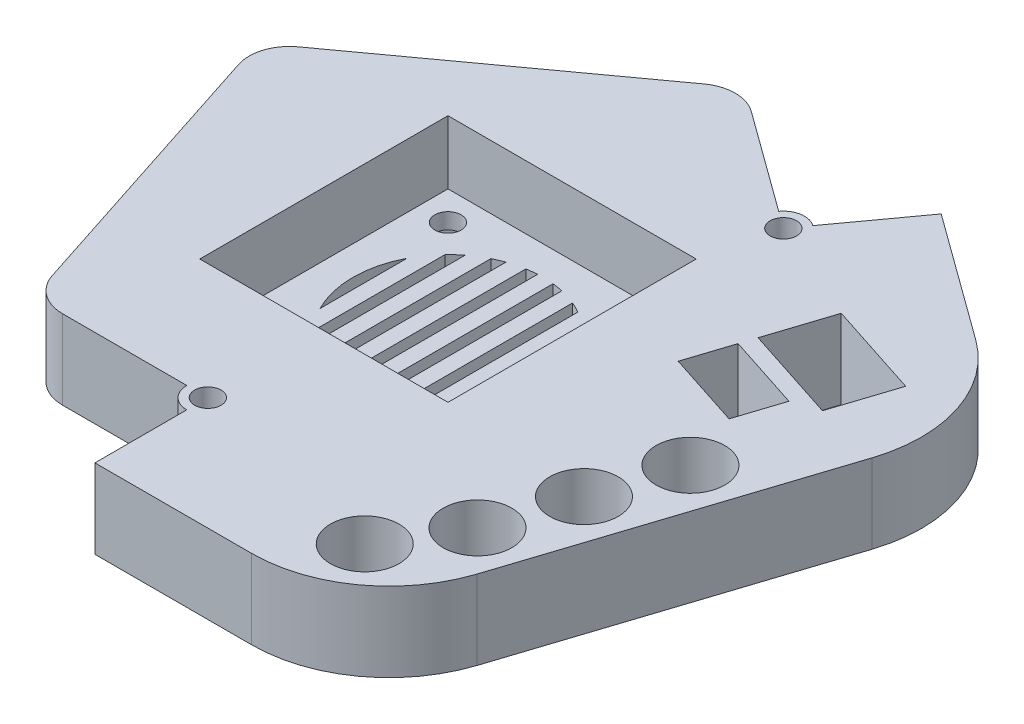
SolidWorks part; units mm, degrees
material "ABS"
ref_plane "Front Plane" through (0, 0, 0) normal (0, 0, 1) x (1, 0, 0)
ref_plane "Top Plane" through (0, 0, 0) normal (0, 1, 0) x (1, 0, 0)
ref_plane "Right Plane" through (0, 0, 0) normal (1, 0, 0) x (0, 0, -1)
sketch "Sketch1" plane through (0, 0, 0) normal (0, 1, 0) x (1, 0, 0)
  line L0 (-12.5926, 0) -> (122.24, 0) construction
  line L1 (-76.5046, 8.789) -> (-56.7275, -52.0787)
  line L2 (-32, -70.0442) -> (32, -70.0442)
  line L3 (56.7275, -52.0787) -> (76.5046, 8.789)
  line L4 (67.0595, 37.8578) -> (15.2824, 75.4761)
  line L5 (-15.2824, 75.4761) -> (-67.0595, 37.8578)
  line L7 (-72.7662, 7.5743) -> (-54.4171, -48.8987)
  line L8 (-29.6896, -66.8642) -> (29.6896, -66.8642)
  line L9 (54.4171, -48.8987) -> (72.7662, 7.5743)
  line L10 (63.3212, 36.6432) -> (15.2824, 71.5454)
  line L11 (-15.2824, 71.5454) -> (-63.3212, 36.6432)
  line L12 (-39.9799, 8.2808) -> (-27.4771, -30.1989)
  line L13 (-20.23, -35.4642) -> (20.23, -35.4642)
  line L14 (27.4771, -30.1989) -> (39.9799, 8.2808)
  line L15 (37.2118, 16.8002) -> (4.4789, 40.582)
  line L16 (-4.4789, 40.582) -> (-37.2118, 16.8002)
  line L17 (-34.7536, 6.5827) -> (-24.2471, -25.7532)
  line L18 (-17, -31.0185) -> (17, -31.0185)
  line L19 (24.2471, -25.7532) -> (34.7536, 6.5827)
  line L20 (31.9855, 15.1021) -> (4.4789, 35.0868)
  line L21 (-4.4789, 35.0868) -> (-31.9855, 15.1021)
  line L22 (-31.0153, 5.3681) -> (-21.9366, -22.5732)
  line L23 (-14.6896, -27.8385) -> (14.6896, -27.8385)
  line L24 (21.9366, -22.5732) -> (31.0153, 5.3681)
  line L25 (28.2472, 13.8875) -> (4.4789, 31.1561)
  line L26 (-4.4789, 31.1561) -> (-28.2472, 13.8875)
  circle A0 centre (0, 0) radius 70.0442 construction
  arc A1 (-56.7275, -52.0787) -> (-32, -70.0442) centre (-32, -44.0442) ccw
  arc A2 (32, -70.0442) -> (56.7275, -52.0787) centre (32, -44.0442) ccw
  arc A3 (76.5046, 8.789) -> (67.0595, 37.8578) centre (51.7771, 16.8234) ccw
  arc A4 (15.2824, 75.4761) -> (-15.2824, 75.4761) centre (0, 54.4417) ccw
  arc A5 (-76.5046, 8.789) -> (-67.0595, 37.8578) centre (-51.7771, 16.8234) cw
  circle A6 centre (0, 0) radius 66.8642 construction
  arc A7 (15.2824, 71.5454) -> (-15.2824, 71.5454) centre (0, 50.511) ccw
  arc A8 (72.7662, 7.5743) -> (63.3212, 36.6432) centre (48.0388, 15.6087) ccw
  arc A9 (29.6896, -66.8642) -> (54.4171, -48.8987) centre (29.6896, -40.8642) ccw
  arc A10 (-72.7662, 7.5743) -> (-63.3212, 36.6432) centre (-48.0388, 15.6087) cw
  arc A11 (-54.4171, -48.8987) -> (-29.6896, -66.8642) centre (-29.6896, -40.8642) ccw
  circle A12 centre (0, 0) radius 35.4642 construction
  circle A13 centre (0, 0) radius 31.0185 construction
  arc A14 (-24.2471, -25.7532) -> (-17, -31.0185) centre (-17, -23.3985) ccw
  arc A15 (17, -31.0185) -> (24.2471, -25.7532) centre (17, -23.3985) ccw
  arc A16 (34.7536, 6.5827) -> (31.9855, 15.1021) centre (27.5066, 8.9374) ccw
  arc A17 (4.4789, 35.0868) -> (-4.4789, 35.0868) centre (0, 28.9221) ccw
  arc A18 (4.4789, 40.582) -> (-4.4789, 40.582) centre (0, 34.4173) ccw
  arc A19 (39.9799, 8.2808) -> (37.2118, 16.8002) centre (32.7328, 10.6355) ccw
  arc A20 (20.23, -35.4642) -> (27.4771, -30.1989) centre (20.23, -27.8442) ccw
  arc A21 (-27.4771, -30.1989) -> (-20.23, -35.4642) centre (-20.23, -27.8442) ccw
  arc A22 (-39.9799, 8.2808) -> (-37.2118, 16.8002) centre (-32.7328, 10.6355) cw
  arc A23 (-34.7536, 6.5827) -> (-31.9855, 15.1021) centre (-27.5066, 8.9374) cw
  circle A24 centre (0, 0) radius 27.8385 construction
  arc A25 (-21.9366, -22.5732) -> (-14.6896, -27.8385) centre (-14.6896, -20.2185) ccw
  arc A26 (14.6896, -27.8385) -> (21.9366, -22.5732) centre (14.6896, -20.2185) ccw
  arc A27 (31.0153, 5.3681) -> (28.2472, 13.8875) centre (23.7683, 7.7228) ccw
  arc A28 (4.4789, 31.1561) -> (-4.4789, 31.1561) centre (0, 24.9914) ccw
  arc A29 (-31.0153, 5.3681) -> (-28.2472, 13.8875) centre (-23.7683, 7.7228) cw
  dimension "D1" = 26
  dimension "D3" = 26
  dimension "D5" = 7.62
  dimension "D8" = 7.62
  dimension "D2" = 64
  dimension "D4" = 3.18
  dimension "D6" = 40.46
  dimension "D7" = 34
  dimension "D9" = 3.18
extrude "Boss-Extrude1" add sketch "Sketch1" along normal blind 10 contours A23 L17 A14 L18 A15 L19 A16 L20 A17 L21 L22 A29 L26 A28 L25 A27 L24 A26 L23 A25 region at (-33.8267, 0, -10.9909)
sketch "Sketch2" plane through (0, 0, 0) normal (0, -1, 0) x (1, 0, 0)
  line L15 (-54.4171, 48.8987) -> (-72.7662, -7.5743)
  line L16 (29.6896, 66.8642) -> (-29.6896, 66.8642)
  line L17 (72.7662, -7.5743) -> (54.4171, 48.8987)
  line L18 (15.2824, -71.5454) -> (63.3212, -36.6432)
  line L19 (-63.3212, -36.6432) -> (-15.2824, -71.5454)
  line L20 (-54.4171, 48.8987) -> (-72.7662, -7.5743)
  line L21 (29.6896, 66.8642) -> (-29.6896, 66.8642)
  line L22 (72.7662, -7.5743) -> (54.4171, 48.8987)
  line L23 (15.2824, -71.5454) -> (63.3212, -36.6432)
  line L24 (-63.3212, -36.6432) -> (-15.2824, -71.5454)
  line L25 (-24.2471, 25.7532) -> (-34.7536, -6.5827)
  line L26 (17, 31.0185) -> (-17, 31.0185)
  line L27 (34.7536, -6.5827) -> (24.2471, 25.7532)
  line L28 (4.4789, -35.0868) -> (31.9855, -15.1021)
  line L29 (-31.9855, -15.1021) -> (-4.4789, -35.0868)
  line L30 (-24.2471, 25.7532) -> (-34.7536, -6.5827)
  line L31 (17, 31.0185) -> (-17, 31.0185)
  line L32 (34.7536, -6.5827) -> (24.2471, 25.7532)
  line L33 (4.4789, -35.0868) -> (31.9855, -15.1021)
  line L34 (-31.9855, -15.1021) -> (-4.4789, -35.0868)
  line L35 (-27.4771, 30.1989) -> (-39.9799, -8.2808)
  line L36 (20.23, 35.4642) -> (-20.23, 35.4642)
  line L37 (39.9799, -8.2808) -> (27.4771, 30.1989)
  line L38 (4.4789, -40.582) -> (37.2118, -16.8002)
  line L39 (-37.2118, -16.8002) -> (-4.4789, -40.582)
  line L40 (-27.4771, 30.1989) -> (-39.9799, -8.2808)
  line L41 (20.23, 35.4642) -> (-20.23, 35.4642)
  line L42 (39.9799, -8.2808) -> (27.4771, 30.1989)
  line L43 (4.4789, -40.582) -> (37.2118, -16.8002)
  line L44 (-37.2118, -16.8002) -> (-4.4789, -40.582)
  line L45 (-21.9366, 22.5732) -> (-31.0153, -5.3681)
  line L46 (14.6896, 27.8385) -> (-14.6896, 27.8385)
  line L47 (31.0153, -5.3681) -> (21.9366, 22.5732)
  line L48 (4.4789, -31.1561) -> (28.2472, -13.8875)
  line L49 (-28.2472, -13.8875) -> (-4.4789, -31.1561)
  line L50 (-21.9366, 22.5732) -> (-31.0153, -5.3681)
  line L51 (14.6896, 27.8385) -> (-14.6896, 27.8385)
  line L52 (31.0153, -5.3681) -> (21.9366, 22.5732)
  line L53 (4.4789, -31.1561) -> (28.2472, -13.8875)
  line L54 (-28.2472, -13.8875) -> (-4.4789, -31.1561)
  arc A15 (-29.6896, 66.8642) -> (-54.4171, 48.8987) centre (-29.6896, 40.8642) ccw
  arc A16 (54.4171, 48.8987) -> (29.6896, 66.8642) centre (29.6896, 40.8642) ccw
  arc A17 (63.3212, -36.6432) -> (72.7662, -7.5743) centre (48.0388, -15.6087) ccw
  arc A18 (-15.2824, -71.5454) -> (15.2824, -71.5454) centre (0, -50.511) ccw
  arc A19 (-72.7662, -7.5743) -> (-63.3212, -36.6432) centre (-48.0388, -15.6087) ccw
  arc A20 (-29.6896, 66.8642) -> (-54.4171, 48.8987) centre (-29.6896, 40.8642) ccw
  arc A21 (54.4171, 48.8987) -> (29.6896, 66.8642) centre (29.6896, 40.8642) ccw
  arc A22 (63.3212, -36.6432) -> (72.7662, -7.5743) centre (48.0388, -15.6087) ccw
  arc A23 (-15.2824, -71.5454) -> (15.2824, -71.5454) centre (0, -50.511) ccw
  arc A24 (-72.7662, -7.5743) -> (-63.3212, -36.6432) centre (-48.0388, -15.6087) ccw
  arc A25 (-17, 31.0185) -> (-24.2471, 25.7532) centre (-17, 23.3985) ccw
  arc A26 (24.2471, 25.7532) -> (17, 31.0185) centre (17, 23.3985) ccw
  arc A27 (31.9855, -15.1021) -> (34.7536, -6.5827) centre (27.5066, -8.9374) ccw
  arc A28 (-4.4789, -35.0868) -> (4.4789, -35.0868) centre (0, -28.9221) ccw
  arc A29 (-34.7536, -6.5827) -> (-31.9855, -15.1021) centre (-27.5066, -8.9374) ccw
  arc A30 (-17, 31.0185) -> (-24.2471, 25.7532) centre (-17, 23.3985) ccw
  arc A31 (24.2471, 25.7532) -> (17, 31.0185) centre (17, 23.3985) ccw
  arc A32 (31.9855, -15.1021) -> (34.7536, -6.5827) centre (27.5066, -8.9374) ccw
  arc A33 (-4.4789, -35.0868) -> (4.4789, -35.0868) centre (0, -28.9221) ccw
  arc A34 (-34.7536, -6.5827) -> (-31.9855, -15.1021) centre (-27.5066, -8.9374) ccw
  arc A35 (-20.23, 35.4642) -> (-27.4771, 30.1989) centre (-20.23, 27.8442) ccw
  arc A36 (27.4771, 30.1989) -> (20.23, 35.4642) centre (20.23, 27.8442) ccw
  arc A37 (37.2118, -16.8002) -> (39.9799, -8.2808) centre (32.7328, -10.6355) ccw
  arc A38 (-4.4789, -40.582) -> (4.4789, -40.582) centre (0, -34.4173) ccw
  arc A39 (-39.9799, -8.2808) -> (-37.2118, -16.8002) centre (-32.7328, -10.6355) ccw
  arc A40 (-20.23, 35.4642) -> (-27.4771, 30.1989) centre (-20.23, 27.8442) ccw
  arc A41 (27.4771, 30.1989) -> (20.23, 35.4642) centre (20.23, 27.8442) ccw
  arc A42 (37.2118, -16.8002) -> (39.9799, -8.2808) centre (32.7328, -10.6355) ccw
  arc A43 (-4.4789, -40.582) -> (4.4789, -40.582) centre (0, -34.4173) ccw
  arc A44 (-39.9799, -8.2808) -> (-37.2118, -16.8002) centre (-32.7328, -10.6355) ccw
  arc A45 (-14.6896, 27.8385) -> (-21.9366, 22.5732) centre (-14.6896, 20.2185) ccw
  arc A46 (21.9366, 22.5732) -> (14.6896, 27.8385) centre (14.6896, 20.2185) ccw
  arc A47 (28.2472, -13.8875) -> (31.0153, -5.3681) centre (23.7683, -7.7228) ccw
  arc A48 (-4.4789, -31.1561) -> (4.4789, -31.1561) centre (0, -24.9914) ccw
  arc A49 (-31.0153, -5.3681) -> (-28.2472, -13.8875) centre (-23.7683, -7.7228) ccw
  arc A50 (-14.6896, 27.8385) -> (-21.9366, 22.5732) centre (-14.6896, 20.2185) ccw
  arc A51 (21.9366, 22.5732) -> (14.6896, 27.8385) centre (14.6896, 20.2185) ccw
  arc A52 (28.2472, -13.8875) -> (31.0153, -5.3681) centre (23.7683, -7.7228) ccw
  arc A53 (-4.4789, -31.1561) -> (4.4789, -31.1561) centre (0, -24.9914) ccw
  arc A54 (-31.0153, -5.3681) -> (-28.2472, -13.8875) centre (-23.7683, -7.7228) ccw
  arc M51 (-34.7536, -6.5827) -> (-31.9855, -15.1021) centre (-27.5066, -8.9374) ccw
  line M52 (-31.9855, -15.1021) -> (-4.4789, -35.0868)
  arc M53 (-4.4789, -35.0868) -> (4.4789, -35.0868) centre (0, -28.9221) ccw
  line M54 (4.4789, -35.0868) -> (31.9855, -15.1021)
  arc M55 (31.9855, -15.1021) -> (34.7536, -6.5827) centre (27.5066, -8.9374) ccw
  line M56 (34.7536, -6.5827) -> (24.2471, 25.7532)
  arc M57 (24.2471, 25.7532) -> (17, 31.0185) centre (17, 23.3985) ccw
  line M58 (17, 31.0185) -> (-17, 31.0185)
  arc M59 (-17, 31.0185) -> (-24.2471, 25.7532) centre (-17, 23.3985) ccw
  line M60 (-24.2471, 25.7532) -> (-34.7536, -6.5827)
  line M61 (-31.0153, -5.3681) -> (-21.9366, 22.5732)
  arc M62 (-21.9366, 22.5732) -> (-14.6896, 27.8385) centre (-14.6896, 20.2185) cw
  line M63 (-14.6896, 27.8385) -> (14.6896, 27.8385)
  arc M64 (14.6896, 27.8385) -> (21.9366, 22.5732) centre (14.6896, 20.2185) cw
  line M65 (21.9366, 22.5732) -> (31.0153, -5.3681)
  arc M66 (31.0153, -5.3681) -> (28.2472, -13.8875) centre (23.7683, -7.7228) cw
  line M67 (28.2472, -13.8875) -> (4.4789, -31.1561)
  arc M68 (4.4789, -31.1561) -> (-4.4789, -31.1561) centre (0, -24.9914) cw
  line M69 (-4.4789, -31.1561) -> (-28.2472, -13.8875)
  arc M70 (-28.2472, -13.8875) -> (-31.0153, -5.3681) centre (-23.7683, -7.7228) cw
  dimension "D2" = 0
  dimension "D3" = 0
  dimension "D4" = 0
  dimension "D5" = 0
extrude "Boss-Extrude2" add sketch "Sketch2" against normal blind 5 contours L20 A24 L24 A23 L23 A22 L22 A21 L21 A20 A44 L40 A40 L41 A41 L42 A42 L43 A43 L44 | A24 L20 A20 L21 A21 L22 A22 L23 A23 L24 | M61 M70 M69 M68 M67 M66 M65 M64 M63 M62 | L40 A44 L44 A43 L43 A42 L42 A41 L41 A40 M51 M60 M59 M58 M57 M56 M55 M54 M53 M52 region at (-43.7605, 0, 60.2312) region at (-24.0512, 0, 33.1037) region at (0, 0, 0)
sketch "Sketch4" plane through (0, 5, 0) normal (0, 1, 0) x (1, 0, 0)
  line L0 (26.7257, 36.7848) -> (39.3018, 54.0943)
  line L1 (-4.4789, 52.948) -> (-48.9725, 20.6215)
  line L2 (-51.7406, 12.1021) -> (-34.7456, -40.2032)
  line L3 (-27.4985, -45.4685) -> (0, -45.4685)
  line L5 (-15.2824, 71.5454) -> (-63.3212, 36.6432)
  line L6 (63.3212, 36.6432) -> (15.2824, 71.5454)
  line L7 (54.4171, -48.8987) -> (72.7662, 7.5743)
  line L8 (-29.6896, -66.8642) -> (29.6896, -66.8642)
  line L9 (-72.7662, 7.5743) -> (-54.4171, -48.8987)
  line L11 (63.3212, 36.6432) -> (39.3018, 54.0943)
  line L12 (54.4171, -48.8987) -> (72.7662, 7.5743)
  line L13 (0, -66.8642) -> (29.6896, -66.8642)
  line L17 (-31.9855, 15.1021) -> (-4.4789, 35.0868) construction
  line L45 (26.7257, 36.7848) -> (4.4789, 52.948)
  line L46 (0, -45.4685) -> (0, -66.8642)
  line L47 (-54.4171, -48.8987) -> (-72.7662, 7.5743) construction
  line L48 (-63.3212, 36.6432) -> (-15.2824, 71.5454) construction
  line L49 (-54.4171, -48.8987) -> (-72.7662, 7.5743)
  line L50 (-63.3212, 36.6432) -> (-15.2824, 71.5454)
  line L51 (39.3018, 54.0943) -> (15.2824, 71.5454)
  line L52 (-29.6896, -66.8642) -> (0, -66.8642)
  line L58 (39.5946, -25.2793) -> (54.3426, 20.1102) [skipped]
  arc A1 (-4.4789, 52.948) -> (4.4789, 52.948) centre (0, 46.7833) cw
  arc A2 (-48.9725, 20.6215) -> (-51.7406, 12.1021) centre (-44.4936, 14.4568) ccw
  arc A3 (-34.7456, -40.2032) -> (-27.4985, -45.4685) centre (-27.4985, -37.8485) ccw
  arc A5 (15.2824, 71.5454) -> (-15.2824, 71.5454) centre (0, 50.511) ccw
  arc A6 (72.7662, 7.5743) -> (63.3212, 36.6432) centre (48.0388, 15.6087) ccw
  arc A7 (29.6896, -66.8642) -> (54.4171, -48.8987) centre (29.6896, -40.8642) ccw
  arc A8 (-54.4171, -48.8987) -> (-29.6896, -66.8642) centre (-29.6896, -40.8642) ccw
  arc A9 (-63.3212, 36.6432) -> (-72.7662, 7.5743) centre (-48.0388, 15.6087) ccw
  arc A11 (72.7662, 7.5743) -> (63.3212, 36.6432) centre (48.0388, 15.6087) ccw
  arc A12 (29.6896, -66.8642) -> (54.4171, -48.8987) centre (29.6896, -40.8642) ccw
  arc A46 (-54.4171, -48.8987) -> (-29.6896, -66.8642) centre (-29.6896, -40.8642) ccw construction
  arc A47 (-63.3212, 36.6432) -> (-72.7662, 7.5743) centre (-48.0388, 15.6087) ccw construction
  arc A48 (15.2824, 71.5454) -> (-15.2824, 71.5454) centre (0, 50.511) ccw construction
  arc A49 (-54.4171, -48.8987) -> (-29.6896, -66.8642) centre (-29.6896, -40.8642) ccw
  arc A50 (-63.3212, 36.6432) -> (-72.7662, 7.5743) centre (-48.0388, 15.6087) ccw
  arc A51 (15.2824, 71.5454) -> (-15.2824, 71.5454) centre (0, 50.511) ccw
  line M41 (-72.7662, 7.5743) -> (-54.4171, -48.8987)
  arc M42 (-54.4171, -48.8987) -> (-29.6896, -66.8642) centre (-29.6896, -40.8642) ccw
  line M43 (-29.6896, -66.8642) -> (29.6896, -66.8642)
  line M47 (63.3212, 36.6432) -> (15.2824, 71.5454)
  arc M48 (15.2824, 71.5454) -> (-15.2824, 71.5454) centre (0, 50.511) ccw
  line M49 (-15.2824, 71.5454) -> (-63.3212, 36.6432)
  arc M50 (-63.3212, 36.6432) -> (-72.7662, 7.5743) centre (-48.0388, 15.6087) ccw
  dimension "D5" = 7.62
  dimension "D2" = 14.45
  dimension "D1" = 0
extrude "Cut-Extrude1" cut sketch "Sketch4" against normal through all contours A3 L2 A2 L1 A1 L45 L0 L46 L3 M47 M48 M49 M50 M41 M42 M43 region at (16.6766, 5, -46.345)
ref_plane "Plane4" through (-51.7406, 5, -12.1021) normal (0.309, 0, 0.9511) x (0.9511, 0, -0.309)
sketch "Sketch6" plane through (0, 5, 0) normal (0, 1, 0) x (1, 0, 0)
  line L7 (63.5917, -20.6622) -> (-51.7406, 16.8115) construction
  line L8 (72.7662, 7.5743) -> (54.4171, -48.8987) construction
  arc A4 (-48.9725, 20.6215) -> (-51.7406, 12.1021) centre (-44.4936, 14.4568) ccw construction
  circle A7 centre (26.7257, 36.7848) radius 4
  circle A8 centre (26.7257, 36.7848) radius 2.5
  circle A9 centre (0, -45.4685) radius 2.5
  circle A10 centre (0, -45.4685) radius 4
sketch "Sketch7" plane through (0, 5, 0) normal (0, 1, 0) x (1, 0, 0)
  line L0 (-12.8062, -18.5) -> (12.8062, -18.5)
  line L1 (22.5, -22.5) -> (-22.5, -22.5)
  line L2 (22.5, -22.5) -> (22.5, 22.5)
  line L3 (22.5, 22.5) -> (-22.5, 22.5)
  line L4 (-22.5, -22.5) -> (-22.5, 22.5)
  line L5 (22.5, -22.5) -> (-22.5, 22.5) construction
  line L6 (22.5, 22.5) -> (-22.5, -22.5) construction
  line L7 (15.8193, -16) -> (-15.8193, -16)
  line L8 (22.5, 0) -> (-22.5, 0) construction
  line L9 (-19.0329, -12) -> (19.0329, -12)
  line L10 (20.3961, -9.5) -> (-20.3961, -9.5)
  line L11 (21.8174, -5.5) -> (-21.8174, -5.5)
  line L12 (22.2991, -3) -> (-22.2991, -3)
  line L13 (22.2991, 3) -> (-22.2991, 3)
  line L14 (15.8193, 16) -> (-15.8193, 16)
  line L15 (-12.8062, 18.5) -> (12.8062, 18.5)
  line L16 (-19.0329, 12) -> (19.0329, 12)
  line L17 (20.3961, 9.5) -> (-20.3961, 9.5)
  line L18 (21.8174, 5.5) -> (-21.8174, 5.5)
  line L19 (63.5917, -20.6622) -> (-51.7406, 16.8115) construction
  line L20 (72.7662, 7.5743) -> (54.4171, -48.8987) construction
  circle A0 centre (0, 0) radius 22.5
  arc A1 (-48.9725, 20.6215) -> (-51.7406, 12.1021) centre (-44.4936, 14.4568) ccw construction
  circle A3 centre (0, -45.4685) radius 4
  circle A5 centre (26.7257, 36.7848) radius 2.5
  circle A7 centre (0, -45.4685) radius 2.5
  circle A9 centre (26.7257, 36.7848) radius 4
  line M15 (39.3018, 54.0943) -> (26.7257, 36.7848)
  line M17 (26.7257, 36.7848) -> (4.4789, 52.948)
  dimension "D5" = 45
  dimension "D6" = 2.5
  dimension "D7" = 4
  dimension "D8" = 4
  dimension "D9" = 2.5
  dimension "D10" = 4
  dimension "D11" = 2.5
extrude "Cut-Extrude2" cut sketch "Sketch7" against normal up to surface (5 mm away) contours L7 A0 L9 | L10 A0 L11 | L12 A0 L13 | L18 A0 L17 | L16 A0 L14 | L15 A0 | A0 L0 | A5 M15 M17 | A7 region at (0, 5, 20.1129) region at (0, 5, 13.9392) region at (0, 5, 7.4777) region at (0, 5, 0) region at (0, 5, -20.1129) region at (0, 5, -7.4777) region at (0, 5, -13.9392) region at (26.804, 5, -36.2908) up to face at (9.1904, 0, 2.9862)
extrude "Boss-Extrude4" add sketch "Sketch6" against normal up to surface (5 mm away) up to face at (0, 0, 0)
sketch "Sketch8" plane through (0, 10, 0) normal (0, 1, 0) x (1, 0, 0)
  line L1 (-46.7527, 39.1607) -> (46.7527, 39.1607)
  line L2 (-46.7527, 39.1607) -> (-46.7527, -39.1607)
  line L3 (-46.7527, -39.1607) -> (46.7527, -39.1607)
  line L4 (46.7527, 39.1607) -> (46.7527, -39.1607)
  line L5 (-46.7527, 39.1607) -> (46.7527, -39.1607) construction
  line L6 (-46.7527, -39.1607) -> (46.7527, 39.1607) construction
  point P0 (0, 0)
extrude "Cut-Extrude3" cut sketch "Sketch8" against normal up to surface (5 mm away) up to face at (0, 5, 0)
sketch "Sketch9" plane through (0, 5, 0) normal (0, 1, 0) x (1, 0, 0)
  line L1 (-4.4789, 35.0868) -> (-31.9855, 15.1021) construction
  line L3 (31.9855, 15.1021) -> (4.4789, 35.0868) construction
  line L4 (24.2471, -25.7532) -> (34.7536, 6.5827) construction
  line L7 (-17, -31.0185) -> (17, -31.0185) construction
  line L9 (-34.7536, 6.5827) -> (-24.2471, -25.7532) construction
  line L11 (-4.4789, 35.0868) -> (-31.9855, 15.1021)
  line L13 (31.9855, 15.1021) -> (4.4789, 35.0868)
  line L14 (24.2471, -25.7532) -> (34.7536, 6.5827)
  line L17 (-17, -31.0185) -> (17, -31.0185)
  line L19 (-34.7536, 6.5827) -> (-24.2471, -25.7532)
  line L21 (36.6878, 16.63) -> (4.4789, 40.0311)
  line L22 (-4.4789, 40.0311) -> (-36.6878, 16.63)
  line L23 (-39.4559, 8.1106) -> (-27.1532, -29.7532)
  line L24 (-19.9062, -35.0185) -> (19.9062, -35.0185)
  line L25 (27.1532, -29.7532) -> (39.4559, 8.1106)
  arc A0 (4.4789, 35.0868) -> (-4.4789, 35.0868) centre (0, 28.9221) ccw construction
  arc A3 (34.7536, 6.5827) -> (31.9855, 15.1021) centre (27.5066, 8.9374) ccw construction
  arc A4 (17, -31.0185) -> (24.2471, -25.7532) centre (17, -23.3985) ccw construction
  arc A6 (-24.2471, -25.7532) -> (-17, -31.0185) centre (-17, -23.3985) ccw construction
  arc A8 (-31.9855, 15.1021) -> (-34.7536, 6.5827) centre (-27.5066, 8.9374) ccw construction
  arc A10 (4.4789, 35.0868) -> (-4.4789, 35.0868) centre (0, 28.9221) ccw
  arc A13 (34.7536, 6.5827) -> (31.9855, 15.1021) centre (27.5066, 8.9374) ccw
  arc A14 (17, -31.0185) -> (24.2471, -25.7532) centre (17, -23.3985) ccw
  arc A16 (-24.2471, -25.7532) -> (-17, -31.0185) centre (-17, -23.3985) ccw
  arc A18 (-31.9855, 15.1021) -> (-34.7536, 6.5827) centre (-27.5066, 8.9374) ccw
  circle A20 centre (0, 0) radius 35.0185 construction
  arc A21 (-27.1532, -29.7532) -> (-19.9062, -35.0185) centre (-19.9062, -27.3985) ccw
  arc A22 (19.9062, -35.0185) -> (27.1532, -29.7532) centre (19.9062, -27.3985) ccw
  arc A23 (36.6878, 16.63) -> (39.4559, 8.1106) centre (32.2089, 10.4653) cw
  arc A24 (4.4789, 40.0311) -> (-4.4789, 40.0311) centre (0, 33.8664) ccw
  arc A25 (-36.6878, 16.63) -> (-39.4559, 8.1106) centre (-32.2089, 10.4653) ccw
  dimension "D1" = 4
  dimension "D2" = 7.62
extrude "Boss-Extrude5" add sketch "Sketch9" against normal blind 32.15
sketch "Sketch12" plane through (0, 0, 0) normal (0, -1, 0) x (1, 0, 0)
  line L0 (35.4321, -25.7098) -> (13.6057, 41.4651)
  line L1 (35.4321, -25.7098) -> (44.6678, -22.7089)
  line L2 (13.6057, 41.4651) -> (22.8414, 44.466)
  line L3 (44.6678, -22.7089) -> (22.8414, 44.466)
  line L5 (24.2471, 25.7532) -> (34.7536, -6.5827) construction
  line L8 (27.4771, 30.1989) -> (39.9799, -8.2808) construction
extrude "Cut-Extrude4" cut sketch "Sketch12" along normal up to next
fillet "Fillet1" radius 10 2 edges at (31.9855, -13.575, -15.1021) (17, -13.575, 31.0185)
sketch "Sketch13" plane through (0, 5, -5) normal (0, -1, 0) x (-1, 0, 0)
  line L6 (-41.3394, 8.5981) -> (-38.5582, 0.0386)
  line L9 (-41.3394, 8.5981) -> (-55.6052, 3.9628)
  line L14 (-38.5582, 0.0386) -> (-52.8241, -4.5967)
  line L15 (-55.6052, 3.9628) -> (-52.8241, -4.5967)
  line L17 (-38.5582, 0.0386) -> (-48.9813, 32.1176) construction
  line L18 (-52.8241, -4.5967) -> (-68.7544, -9.7728) construction
  line L19 (-52.8241, -4.5967) -> (-30.9779, -71.8323) construction
  line L20 (-42.2664, 11.4512) -> (-46.1292, 23.3395)
  line L21 (-59.7194, -6.8371) -> (-17.9822, -135.2911) construction
  line L22 (-72.7662, 2.5743) -> (-54.4171, -53.8987) construction
  line L26 (-54.4171, -53.8987) -> (-45.382, -50.963) construction
  line L27 (-29.6896, -71.8642) -> (-29.6896, -62.3642)
  line L28 (-38.8328, -59.5993) -> (-46.8952, -46.306) construction
  line L29 (-42.2664, 11.4512) -> (-60.3365, 5.5799)
  line L30 (-46.1292, 23.3395) -> (-64.1992, 17.4681)
  line L31 (-60.3365, 5.5799) -> (-64.1992, 17.4681)
  circle A6 centre (-56.7837, -15.8721) radius 6.5
  circle A7 centre (-51.8395, -31.0891) radius 6.5
  circle A12 centre (-46.8952, -46.306) radius 6.5
  arc A14 (-45.382, -50.963) -> (-29.6896, -62.3642) centre (-29.6896, -45.8642) ccw
  circle A15 centre (-38.8328, -59.5993) radius 6.5
  point P0 (-270.9923, 22.204)
  point P2 (-54.4171, -53.8987)
  point P10 (-39.1728, -70.0731)
  point P17 (-54.9321, -52.3136)
  point P23 (0, 0)
  point P32 (0, 0)
  point P36 (0, 0)
  dimension "D1" = 9.5
extrude "Cut-Extrude6" cut sketch "Sketch13" along normal blind 10 contours L29 L31 L30 L20 | L15 L9 L6 L14 | A6 | A7 | A12 | A15 | A15 region at (47.0817, 5, -7.0007) region at (53.2328, 5, -19.4597) region at (56.7837, 5, 10.8721) region at (51.8395, 5, 26.0891) region at (46.8952, 5, 41.306) region at (37.1836, 5, 52.1219) region at (40.2265, 5, 56.6931)
sketch "Sketch17" plane through (0, 5, 0) normal (0, 1, 0) x (1, 0, 0)
  line L0 (22.2991, 3) -> (-22.2991, 3) construction
  line L1 (24.0637, -24.6394) -> (-34.1681, -24.6394)
  line L2 (24.0637, -24.6394) -> (24.0637, 30.6394)
  line L3 (24.0637, 30.6394) -> (-34.1681, 30.6394)
  line L4 (-34.1681, -24.6394) -> (-34.1681, 30.6394)
  line L5 (24.0637, -24.6394) -> (-34.1681, 30.6394) construction
  line L6 (24.0637, 30.6394) -> (-34.1681, -24.6394) construction
  point P0 (-5.0522, 3)
extrude "Boss-Extrude6" add sketch "Sketch17" against normal up to surface (5 mm away) up to face at (0, 0, 0)
sketch "Sketch18" plane through (0, 5, 0) normal (0, -1, 0) x (1, 0, 0)
  line L0 (-33.3046, 10.8213) -> (33.5322, -10.8953) construction
  line L1 (-39.4559, -8.1106) -> (-27.1532, 29.7532) construction
  line L2 (0, -41.4864) -> (0, 26.004) construction
  line L3 (-23.5, 0) -> (23.5, 0) construction
  line L8 (23.5, 0) -> (0, 23.5) construction
  line L9 (0, 23.5) -> (0, -23.5) construction
  line L10 (-16, 8.2462) -> (-16, -8.2462)
  line L11 (18, -18) -> (-18, -18)
  line L12 (18, -18) -> (18, 18)
  line L13 (18, 18) -> (-18, 18)
  line L14 (-18, -18) -> (-18, 18)
  line L15 (18, -18) -> (-18, 18) construction
  line L16 (18, 18) -> (-18, -18) construction
  line L17 (-13, 12.4499) -> (-13, -12.4499)
  line L18 (-8, -16.1245) -> (-8, 16.1245)
  line L19 (-11, 14.2478) -> (-11, -14.2478)
  line L20 (-6, -16.9706) -> (-6, 16.9706)
  line L21 (-3, -17.7482) -> (-3, 17.7482)
  line L22 (2, -17.8885) -> (2, 17.8885)
  line L23 (14, 11.3137) -> (14, -11.3137)
  line L25 (12, 13.4164) -> (12, -13.4164)
  line L27 (9, 15.5885) -> (9, -15.5885)
  line L28 (7, -16.5831) -> (7, 16.5831)
  line L29 (4, -17.5499) -> (4, 17.5499)
  line L30 (-1, 17.9722) -> (-1, -17.9722)
  line L31 (17, -5.9161) -> (17, 5.9161)
  arc A6 (-4.4789, -40.0311) -> (4.4789, -40.0311) centre (0, -33.8664) ccw construction
  circle A7 centre (-18, 18) radius 2.5
  circle A8 centre (18, 18) radius 2.5
  circle A9 centre (18, -18) radius 2.5
  circle A10 centre (-18, -18) radius 2.5
  circle A11 centre (0, 0) radius 18
  point P13 (0, 0)
  point P32 (-18, 0)
  dimension "D2" = 5
  dimension "D1" = 36
  dimension "D3" = 2
  dimension "D4" = 3
  dimension "D5" = 2
  dimension "D6" = 3
  dimension "D7" = 2
  dimension "D8" = 3
  dimension "D9" = 2
  dimension "D10" = 3
  dimension "D11" = 2
  dimension "D12" = 3
  dimension "D13" = 2
  dimension "D14" = 3
  dimension "D15" = 2
  dimension "D16" = 3
sketch "Sketch19" plane through (0, 5, 0) normal (0, 1, 0) x (1, 0, 0)
  line L4 (60.3365, 10.5799) -> (64.1992, 22.4681)
  line L5 (42.2664, 16.4512) -> (60.3365, 10.5799)
  line L6 (46.1292, 28.3395) -> (42.2664, 16.4512)
  line L7 (64.1992, 22.4681) -> (46.1292, 28.3395)
  line L8 (60.3365, 10.5799) -> (64.1992, 22.4681)
  line L9 (42.2664, 16.4512) -> (60.3365, 10.5799)
  line L10 (46.1292, 28.3395) -> (42.2664, 16.4512)
  line L11 (64.1992, 22.4681) -> (46.1292, 28.3395)
  line L12 (52.8241, 0.4033) -> (55.6052, 8.9628)
  line L13 (38.5582, 5.0386) -> (52.8241, 0.4033)
  line L14 (41.3394, 13.5981) -> (38.5582, 5.0386)
  line L15 (55.6052, 8.9628) -> (41.3394, 13.5981)
  line L16 (52.8241, 0.4033) -> (55.6052, 8.9628)
  line L17 (38.5582, 5.0386) -> (52.8241, 0.4033)
  line L18 (41.3394, 13.5981) -> (38.5582, 5.0386)
  line L19 (55.6052, 8.9628) -> (41.3394, 13.5981)
  line L25 (-51.7406, 12.1021) -> (-34.7456, -40.2032)
  line L26 (-27.4985, -45.4685) -> (-4, -45.4685)
  line L27 (0, -49.4685) -> (0, -66.8642)
  line L28 (0, -66.8642) -> (29.6896, -66.8642)
  line L29 (54.4171, -48.8987) -> (72.7662, 7.5743)
  line L30 (63.3212, 36.6432) -> (39.3018, 54.0943)
  line L31 (39.3018, 54.0943) -> (29.0769, 40.0209)
  line L32 (23.4896, 39.1359) -> (4.4789, 52.948)
  line L33 (-4.4789, 52.948) -> (-48.9725, 20.6215)
  line L34 (-51.7406, 12.1021) -> (-34.7456, -40.2032)
  line L35 (-27.4985, -45.4685) -> (-4, -45.4685)
  line L36 (0, -49.4685) -> (0, -66.8642)
  line L37 (0, -66.8642) -> (29.6896, -66.8642)
  line L38 (54.4171, -48.8987) -> (72.7662, 7.5743)
  line L39 (63.3212, 36.6432) -> (39.3018, 54.0943)
  line L40 (39.3018, 54.0943) -> (29.0769, 40.0209)
  line L41 (23.4896, 39.1359) -> (4.4789, 52.948)
  line L42 (-4.4789, 52.948) -> (-48.9725, 20.6215)
  circle A1 centre (26.7257, 36.7848) radius 2.5
  circle A2 centre (26.7257, 36.7848) radius 2.5
  circle A3 centre (0, -45.4685) radius 2.5
  circle A4 centre (0, -45.4685) radius 2.5
  circle A5 centre (56.7837, -10.8721) radius 6.5
  circle A6 centre (56.7837, -10.8721) radius 6.5
  circle A7 centre (51.8395, -26.0891) radius 6.5
  circle A8 centre (51.8395, -26.0891) radius 6.5
  circle A9 centre (46.8952, -41.306) radius 6.5
  circle A10 centre (46.8952, -41.306) radius 6.5
  circle A11 centre (38.8328, -54.5993) radius 6.5
  circle A12 centre (38.8328, -54.5993) radius 6.5
  arc A19 (-34.7456, -40.2032) -> (-27.4985, -45.4685) centre (-27.4985, -37.8485) ccw
  arc A20 (-4, -45.4685) -> (0, -49.4685) centre (0, -45.4685) ccw
  arc A21 (29.6896, -66.8642) -> (54.4171, -48.8987) centre (29.6896, -40.8642) ccw
  arc A22 (72.7662, 7.5743) -> (63.3212, 36.6432) centre (48.0388, 15.6087) ccw
  arc A23 (29.0769, 40.0209) -> (23.4896, 39.1359) centre (26.7257, 36.7848) ccw
  arc A24 (4.4789, 52.948) -> (-4.4789, 52.948) centre (0, 46.7833) ccw
  arc A25 (-48.9725, 20.6215) -> (-51.7406, 12.1021) centre (-44.4936, 14.4568) ccw
  arc A26 (-34.7456, -40.2032) -> (-27.4985, -45.4685) centre (-27.4985, -37.8485) ccw
  arc A27 (-4, -45.4685) -> (0, -49.4685) centre (0, -45.4685) ccw
  arc A28 (29.6896, -66.8642) -> (54.4171, -48.8987) centre (29.6896, -40.8642) ccw
  arc A29 (72.7662, 7.5743) -> (63.3212, 36.6432) centre (48.0388, 15.6087) ccw
  arc A30 (29.0769, 40.0209) -> (23.4896, 39.1359) centre (26.7257, 36.7848) ccw
  arc A31 (4.4789, 52.948) -> (-4.4789, 52.948) centre (0, 46.7833) ccw
  arc A32 (-48.9725, 20.6215) -> (-51.7406, 12.1021) centre (-44.4936, 14.4568) ccw
  dimension "D1" = 0
  dimension "D2" = 0
  dimension "D3" = 0
  dimension "D4" = 0
  dimension "D5" = 0
  dimension "D6" = 0
  dimension "D7" = 0
  dimension "D8" = 0
  dimension "D9" = 0
extrude "Boss-Extrude7" add sketch "Sketch19" along normal blind 10
sketch "Sketch20" plane through (0, 0, 0) normal (0, 1, 0) x (1, 0, 0)
  line L0 (-33.3046, 10.8213) -> (33.5322, -10.8953) construction
  line L1 (0, -41.4864) -> (0, 26.004) construction
  line L2 (-23.5, 0) -> (23.5, 0) construction
  line L3 (23.5, 0) -> (0, 23.5) construction
  line L4 (0, 23.5) -> (0, -23.5) construction
  line L5 (-16, 8.2462) -> (-16, -8.2462)
  line L6 (18, -18) -> (-18, -18)
  line L7 (18, -18) -> (18, 18)
  line L8 (18, 18) -> (-18, 18)
  line L9 (-18, -18) -> (-18, 18)
  line L10 (18, -18) -> (-18, 18) construction
  line L11 (18, 18) -> (-18, -18) construction
  line L12 (-13, 12.4499) -> (-13, -12.4499)
  line L13 (-8, -16.1245) -> (-8, 16.1245)
  line L14 (-11, 14.2478) -> (-11, -14.2478)
  line L15 (-6, -16.9706) -> (-6, 16.9706)
  line L16 (-3, -17.7482) -> (-3, 17.7482)
  line L17 (2, -17.8885) -> (2, 17.8885)
  line L18 (14, 11.3137) -> (14, -11.3137)
  line L19 (12, 13.4164) -> (12, -13.4164)
  line L20 (9, 15.5885) -> (9, -15.5885)
  line L21 (7, -16.5831) -> (7, 16.5831)
  line L22 (4, -17.5499) -> (4, 17.5499)
  line L23 (-1, 17.9722) -> (-1, -17.9722)
  line L24 (17, -5.9161) -> (17, 5.9161)
  circle A0 centre (-18, 18) radius 2.5
  circle A1 centre (18, 18) radius 2.5
  circle A2 centre (18, -18) radius 2.5
  circle A3 centre (-18, -18) radius 2.5
  circle A4 centre (0, 0) radius 18
  point P8 (0, 0)
sketch "Sketch24" plane through (0, 15, 0) normal (0, 1, 0) x (1, 0, 0)
  line L1 (23.5, -23.5) -> (-23.5, -23.5)
  line L2 (23.5, -23.5) -> (23.5, 23.5)
  line L3 (23.5, 23.5) -> (-23.5, 23.5)
  line L4 (-23.5, -23.5) -> (-23.5, 23.5)
  line L5 (23.5, -23.5) -> (-23.5, 23.5) construction
  line L6 (23.5, 23.5) -> (-23.5, -23.5) construction
  point P0 (0, 0)
  dimension "D1" = 47
extrude "Cut-Extrude9" cut sketch "Sketch24" against normal blind 12
extrude "Cut-Extrude11" cut sketch "Sketch20" along normal blind 5 contours A4 L5 | A4 L14 L12 | A4 L15 L13 | A4 L23 L16 | A4 L17 L22 | A4 L21 L20 | A4 L19 L18 | A4 L24 | A2 L7 L6 | A2 L6 L7 | A3 L6 L9 | A3 L9 L6 | A0 L8 L9 | A0 L9 L8 | A1 L7 L8 | A1 L8 L7 region at (-16.8039, 0, 0) region at (-11.9777, 0, 0) region at (-16.939, 0, 16.939) region at (-18.3537, 0, 18.3537) region at (-18.3537, 0, -18.3537) region at (-16.939, 0, -16.939) region at (-6.9915, 0, 0) region at (-1.9979, 0, 0) region at (16.939, 0, 16.939) region at (18.3537, 0, 18.3537) region at (2.9968, 0, 0) region at (18.3537, 0, -18.3537) region at (16.939, 0, -16.939) region at (17.401, 0, 0) region at (7.9897, 0, 0) region at (12.9719, 0, 0)
